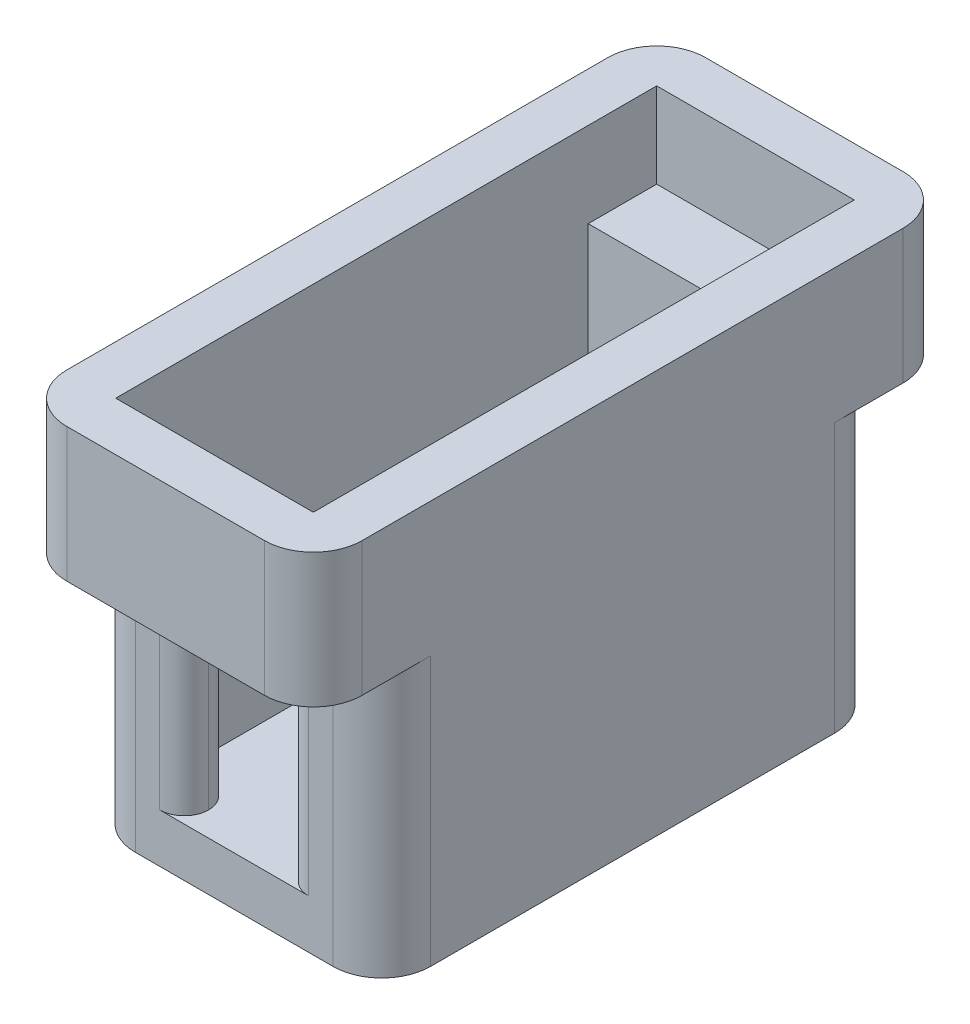
SolidWorks part; units mm, degrees
ref_plane "Front Plane" through (0, 0, 0) normal (0, 0, 1) x (1, 0, 0)
ref_plane "Top Plane" through (0, 0, 0) normal (0, 1, 0) x (1, 0, 0)
ref_plane "Right Plane" through (0, 0, 0) normal (1, 0, 0) x (0, 0, -1)
sketch "Sketch1" plane through (0, 0, 0) normal (0, 1, 0) x (1, 0, 0)
  line L1 (15.1, -25.65) -> (-15.1, -25.65)
  line L2 (15.1, -25.65) -> (15.1, 25.65)
  line L3 (15.1, 25.65) -> (-15.1, 25.65)
  line L4 (-15.1, -25.65) -> (-15.1, 25.65)
  line L5 (15.1, -25.65) -> (-15.1, 25.65) construction
  line L6 (15.1, 25.65) -> (-15.1, -25.65) construction
  point P0 (0, 0)
  dimension "D1" = 51.3
  dimension "D2" = 30.2
extrude "Boss-Extrude1" add sketch "Sketch1" along normal blind 5
sketch "Sketch2" plane through (0, 5, 0) normal (0, 1, 0) x (1, 0, 0)
  line L0 (5.1, -20.65) -> (5.1, -25.65)
  line L1 (15.1, -25.65) -> (-15.1, -25.65)
  line L2 (15.1, -25.65) -> (15.1, 25.65)
  line L3 (15.1, 25.65) -> (-15.1, 25.65)
  line L4 (-15.1, -25.65) -> (-15.1, 25.65)
  line L5 (15.1, -25.65) -> (-15.1, 25.65) construction
  line L6 (15.1, 25.65) -> (-15.1, -25.65) construction
  line L7 (10.1, -20.65) -> (-10.1, -20.65)
  line L8 (10.1, -20.65) -> (10.1, 20.65)
  line L9 (10.1, 20.65) -> (-10.1, 20.65)
  line L10 (-10.1, -20.65) -> (-10.1, 20.65)
  line L11 (10.1, -20.65) -> (-10.1, 20.65) construction
  line L12 (10.1, 20.65) -> (-10.1, -20.65) construction
  line L13 (-5.1, -20.65) -> (-5.1, -25.65)
  point P0 (0, 0)
  point P7 (0, 0)
  line M10 (-15.1, 25.65) -> (-15.1, -25.65)
  line M11 (-15.1, -25.65) -> (15.1, -25.65)
  line M12 (15.1, -25.65) -> (15.1, 25.65)
  line M13 (15.1, 25.65) -> (-15.1, 25.65)
  dimension "D1" = 41.3
  dimension "D2" = 20.2
  dimension "D3" = 5
  dimension "D4" = 5
extrude "Boss-Extrude2" add sketch "Sketch2" along normal blind 27.5 contours L13 L7 L10 L9 L8 L0 M11 M12 M13 M10 region at (7.6, 5, 21.2453)
sketch "Sketch3" plane through (0, 0, 25.65) normal (0, 0, 1) x (1, 0, 0)
  line L0 (15.1, 32.5) -> (15.1, 0) construction
  line L1 (-15.1, 32.5) -> (15.1, 32.5)
  line L2 (-15.1, 32.5) -> (-15.1, 27.5)
  line L3 (-15.1, 27.5) -> (15.1, 27.5)
  line L4 (15.1, 32.5) -> (15.1, 27.5)
  dimension "D1" = 5
extrude "Boss-Extrude3" add sketch "Sketch3" along normal blind 7
sketch "Sketch4" plane through (0, 0, -25.65) normal (0, 0, -1) x (-1, 0, 0)
  line L0 (15.1, 32.5) -> (15.1, 0) construction
  line L1 (-15.1, 32.5) -> (15.1, 32.5)
  line L2 (-15.1, 32.5) -> (-15.1, 27.5)
  line L3 (-15.1, 27.5) -> (15.1, 27.5)
  line L4 (15.1, 32.5) -> (15.1, 27.5)
  dimension "D1" = 5
extrude "Boss-Extrude4" add sketch "Sketch4" along normal blind 7
sketch "Sketch5" plane through (0, 32.5, 0) normal (0, 1, 0) x (1, 0, 0)
  line L1 (-15.1, 32.65) -> (15.1, 32.65)
  line L2 (-15.1, 32.65) -> (-15.1, -32.65)
  line L3 (-15.1, -32.65) -> (15.1, -32.65)
  line L4 (15.1, 32.65) -> (15.1, -32.65)
  line L5 (10.1, -27.65) -> (-10.1, -27.65)
  line L6 (10.1, -27.65) -> (10.1, 27.65)
  line L7 (10.1, 27.65) -> (-10.1, 27.65)
  line L8 (-10.1, -27.65) -> (-10.1, 27.65)
  line L9 (10.1, -27.65) -> (-10.1, 27.65) construction
  line L10 (10.1, 27.65) -> (-10.1, -27.65) construction
  point P6 (0, 0)
  dimension "D1" = 5
  dimension "D2" = 5
extrude "Boss-Extrude5" add sketch "Sketch5" along normal blind 8.7
fillet "Fillet1" radius 5 8 edges at (-15.1, 34.35, 32.65) (15.1, 34.35, 32.65) (15.1, 34.35, -32.65) (-15.1, 34.35, -32.65) (15.1, 13.75, -25.65) (-15.1, 13.75, -25.65) (15.1, 13.75, 25.65) (-15.1, 13.75, 25.65)
fillet "Fillet2" radius 2.5 4 edges at (-5.1, 16.25, 25.65) (5.1, 16.25, 25.65) (-5.1, 18.75, 20.65) (5.1, 18.75, 20.65)
fillet "Fillet3" radius 2.5 2 edges at (-5.1, 30, 25.65) (5.1, 30, 25.65)
